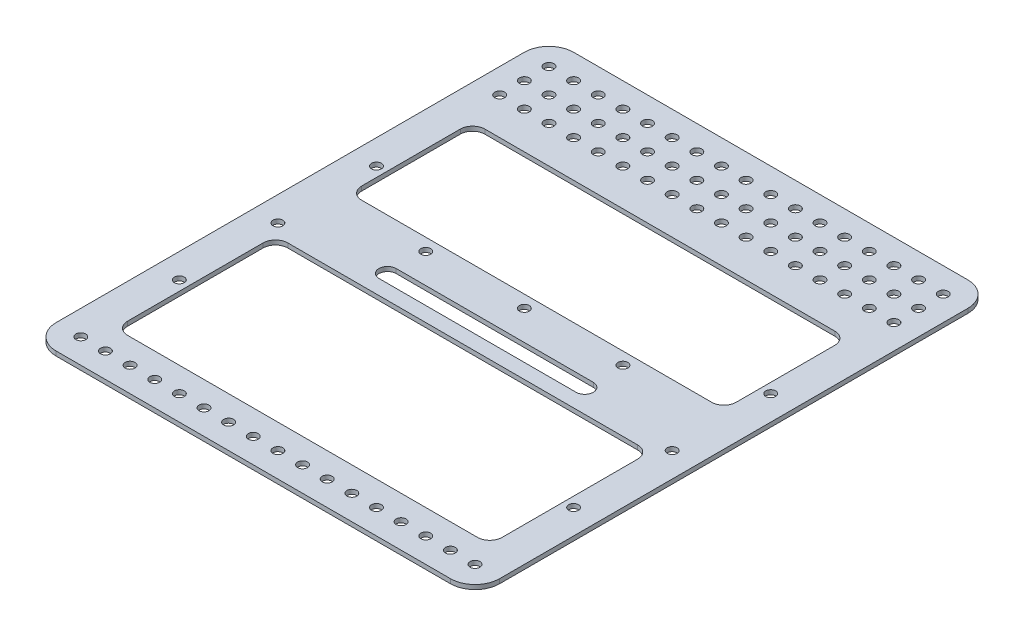
SolidWorks part; units mm, degrees
ref_plane "Front Plane" through (0, 0, 0) normal (0, 0, 1) x (1, 0, 0)
ref_plane "Top Plane" through (0, 0, 0) normal (0, 1, 0) x (1, 0, 0)
ref_plane "Right Plane" through (0, 0, 0) normal (1, 0, 0) x (0, 0, -1)
sketch "Sketch3" plane through (0, 0, 0) normal (0, 1, 0) x (1, 0, 0)
  line B0 (0, 0) -> (228.6, 0)
  line B1 (0, 0) -> (0, 266.7)
  line B2 (0, 266.7) -> (228.6, 266.7)
  line B3 (228.6, 0) -> (228.6, 266.7)
  line B4 (24.13, 101.6) -> (204.47, 101.6) construction
  line B5 (24.13, 101.6) -> (24.13, 25.4) construction
  line B6 (204.47, 101.6) -> (204.47, 25.4) construction
  line B7 (17.78, 107.95) -> (17.78, 25.4)
  line B8 (17.78, 107.95) -> (210.82, 107.95)
  line B9 (210.82, 107.95) -> (210.82, 25.4)
  line B10 (17.78, 127) -> (210.82, 127)
  line B11 (17.78, 127) -> (17.78, 209.55)
  line B12 (17.78, 209.55) -> (210.82, 209.55)
  line B13 (210.82, 127) -> (210.82, 209.55)
  circle B14 centre (12.7, 254) radius 2.54
  circle B15 centre (25.4, 254) radius 2.54
  circle B16 centre (38.1, 254) radius 2.54
  circle B17 centre (50.8, 254) radius 2.54
  circle B18 centre (63.5, 254) radius 2.54
  circle B19 centre (76.2, 254) radius 2.54
  circle B20 centre (88.9, 254) radius 2.54
  circle B21 centre (101.6, 254) radius 2.54
  circle B22 centre (114.3, 254) radius 2.54
  circle B23 centre (127, 254) radius 2.54
  circle B24 centre (139.7, 254) radius 2.54
  circle B25 centre (152.4, 254) radius 2.54
  circle B26 centre (165.1, 254) radius 2.54
  circle B27 centre (177.8, 254) radius 2.54
  circle B28 centre (190.5, 254) radius 2.54
  circle B29 centre (203.2, 254) radius 2.54
  circle B30 centre (215.9, 254) radius 2.54
  circle B31 centre (25.4, 241.3) radius 2.54
  circle B32 centre (38.1, 241.3) radius 2.54
  circle B33 centre (50.8, 241.3) radius 2.54
  circle B34 centre (63.5, 241.3) radius 2.54
  circle B35 centre (76.2, 241.3) radius 2.54
  circle B36 centre (88.9, 241.3) radius 2.54
  circle B37 centre (101.6, 241.3) radius 2.54
  circle B38 centre (114.3, 241.3) radius 2.54
  circle B39 centre (127, 241.3) radius 2.54
  circle B40 centre (139.7, 241.3) radius 2.54
  circle B41 centre (152.4, 241.3) radius 2.54
  circle B42 centre (165.1, 241.3) radius 2.54
  circle B43 centre (177.8, 241.3) radius 2.54
  circle B44 centre (190.5, 241.3) radius 2.54
  circle B45 centre (203.2, 241.3) radius 2.54
  circle B46 centre (215.9, 241.3) radius 2.54
  circle B47 centre (25.4, 228.6) radius 2.54
  circle B48 centre (38.1, 228.6) radius 2.54
  circle B49 centre (50.8, 228.6) radius 2.54
  circle B50 centre (63.5, 228.6) radius 2.54
  circle B51 centre (76.2, 228.6) radius 2.54
  circle B52 centre (88.9, 228.6) radius 2.54
  circle B53 centre (101.6, 228.6) radius 2.54
  circle B54 centre (114.3, 228.6) radius 2.54
  circle B55 centre (127, 228.6) radius 2.54
  circle B56 centre (139.7, 228.6) radius 2.54
  circle B57 centre (152.4, 228.6) radius 2.54
  circle B58 centre (165.1, 228.6) radius 2.54
  circle B59 centre (177.8, 228.6) radius 2.54
  circle B60 centre (190.5, 228.6) radius 2.54
  circle B61 centre (203.2, 228.6) radius 2.54
  circle B62 centre (215.9, 228.6) radius 2.54
  circle B63 centre (12.7, 241.3) radius 2.54
  circle B64 centre (12.7, 228.6) radius 2.54
  circle B65 centre (12.7, 12.7) radius 2.54
  circle B66 centre (25.4, 12.7) radius 2.54
  circle B67 centre (38.1, 12.7) radius 2.54
  circle B68 centre (50.8, 12.7) radius 2.54
  circle B69 centre (63.5, 12.7) radius 2.54
  circle B70 centre (76.2, 12.7) radius 2.54
  circle B71 centre (88.9, 12.7) radius 2.54
  circle B72 centre (101.6, 12.7) radius 2.54
  circle B73 centre (114.3, 12.7) radius 2.54
  circle B74 centre (127, 12.7) radius 2.54
  circle B75 centre (139.7, 12.7) radius 2.54
  circle B76 centre (152.4, 12.7) radius 2.54
  circle B77 centre (165.1, 12.7) radius 2.54
  circle B78 centre (177.8, 12.7) radius 2.54
  circle B79 centre (190.5, 12.7) radius 2.54
  circle B80 centre (203.2, 12.7) radius 2.54
  circle B81 centre (215.9, 12.7) radius 2.54
  circle B82 centre (12.7, 114.3) radius 2.54
  circle B83 centre (63.5, 114.3) radius 2.54
  circle B84 centre (114.3, 114.3) radius 2.54
  circle B85 centre (165.1, 114.3) radius 2.54
  circle B86 centre (215.9, 114.3) radius 2.54
  circle B87 centre (12.7, 165.1) radius 2.54
  circle B88 centre (215.9, 165.1) radius 2.54
  circle B89 centre (12.7, 63.5) radius 2.54
  circle B90 centre (215.9, 63.5) radius 2.54
  line B91 (17.78, 25.4) -> (210.82, 25.4)
sketch_block_instance "Block-Battery Holder-1"
sketch_block "Block-Battery Holder" parameters "D5"=5.08, "D10"=5.08, "D13"=5.08, "D1"=228.6, "D2"=19.05, "D3"=12.7, "D4"=12.7, "D6"=12.7, "D7"=12.7, "D8"=12.7, "D9"=12.7, "D11"=12.7, "D12"=12.7, "D14"=50.8, "D15"=50.8, "D16"=50.8, "D17"=76.2
extrude "Boss-Extrude3" add sketch "Sketch3" along normal blind 2.286
sketch "Sketch6" plane through (0, 2.286, 0) normal (0, 1, 0) x (1, 0, 0)
  line L0 (17.78, 209.55) -> (17.78, 127) construction
  line L1 (210.82, 127) -> (17.78, 127)
  line L2 (210.82, 127) -> (210.82, 146.05)
  line L3 (210.82, 146.05) -> (17.78, 146.05)
  line L4 (17.78, 127) -> (17.78, 146.05)
  dimension "D1" = 19.05
extrude "Boss-Extrude4" add sketch "Sketch6" against normal up to surface (2.286 mm away) up to face at (12.7, 0, -60.96)
sketch "Sketch8" plane through (0, 2.286, 0) normal (0, 1, 0) x (1, 0, 0)
  circle A0 centre (63.5, 114.3) radius 2.54 construction
  circle A1 centre (114.3, 114.3) radius 2.54 construction
  circle A2 centre (165.1, 114.3) radius 2.54 construction
  circle A3 centre (63.5, 114.3) radius 2.54
  circle A4 centre (114.3, 114.3) radius 2.54
  circle A5 centre (165.1, 114.3) radius 2.54
extrude "Boss-Extrude5" add sketch "Sketch8" against normal through all
sketch "Sketch9" plane through (0, 2.286, 0) normal (0, 1, 0) x (1, 0, 0)
  line L1 (210.82, 107.95) -> (17.78, 107.95) construction
  line L2 (165.1, 120.015) -> (63.5, 120.015) construction
  line L3 (165.1, 115.57) -> (63.5, 115.57)
  line L4 (165.1, 124.46) -> (63.5, 124.46)
  line L6 (210.82, 146.05) -> (210.82, 209.55) construction
  line L7 (210.82, 146.05) -> (17.78, 146.05) construction
  circle A0 centre (165.1, 139.7) radius 2.54
  circle A1 centre (114.3, 139.7) radius 2.54
  arc A4 (165.1, 115.57) -> (165.1, 124.46) centre (165.1, 120.015) ccw
  circle A5 centre (63.5, 139.7) radius 2.54
  arc A6 (63.5, 124.46) -> (63.5, 115.57) centre (63.5, 120.015) ccw
  point P6 (114.3, 120.015)
  dimension "D1" = 5.08
  dimension "D2" = 7.62
  dimension "D3" = 45.72
  dimension "D4" = 50.8
  dimension "D5" = 50.8
  dimension "D6" = 5.08
  dimension "D7" = 6.35
  dimension "D8" = 8.89
extrude "Cut-Extrude2" cut sketch "Sketch9" against normal through all
fillet "Fillet5" radius 12.7 4 edges at (0, 1.143, -266.7) (228.6, 1.143, -266.7) (228.6, 1.143, 0) (0, 1.143, 0)
fillet "Fillet6" radius 6.35 8 edges at (210.82, 1.143, -209.55) (17.78, 1.143, -209.55) (17.78, 1.143, -107.95) (17.78, 1.143, -25.4) (210.82, 1.143, -25.4) (210.82, 1.143, -107.95) (17.78, 1.143, -146.05) (210.82, 1.143, -146.05)
sketch "Sketch4" plane through (0, 0, 0) normal (0, -1, 0) x (1, 0, 0)
  line L0 (-1000, 0) -> (49000, 0) construction
  line L1 (0, -1000) -> (0, 49000) construction
  point P4 (0, 0)
sketch "Sketch5" plane through (0, 0, 0) normal (0, -1, 0) x (1, 0, 0)
  line L0 (204.47, -209.55) -> (24.13, -209.55) construction
  line L1 (17.78, -203.2) -> (17.78, -152.4) construction
  line L2 (55.88, -171.45) -> (170.18, -171.45) construction
  line L3 (55.88, -171.45) -> (55.88, -57.15) construction
  circle A0 centre (55.88, -171.45) radius 2.54
  circle A1 centre (170.18, -171.45) radius 2.54
  circle A2 centre (170.18, -57.15) radius 2.54
  circle A3 centre (55.88, -57.15) radius 2.54
  dimension "D1" = 38.1
  dimension "D2" = 38.1
  dimension "D3" = 5.08
  dimension "D6" = 114.3
  dimension "D7" = 114.3
  dimension "D4" = 2
  dimension "D5" = 2
